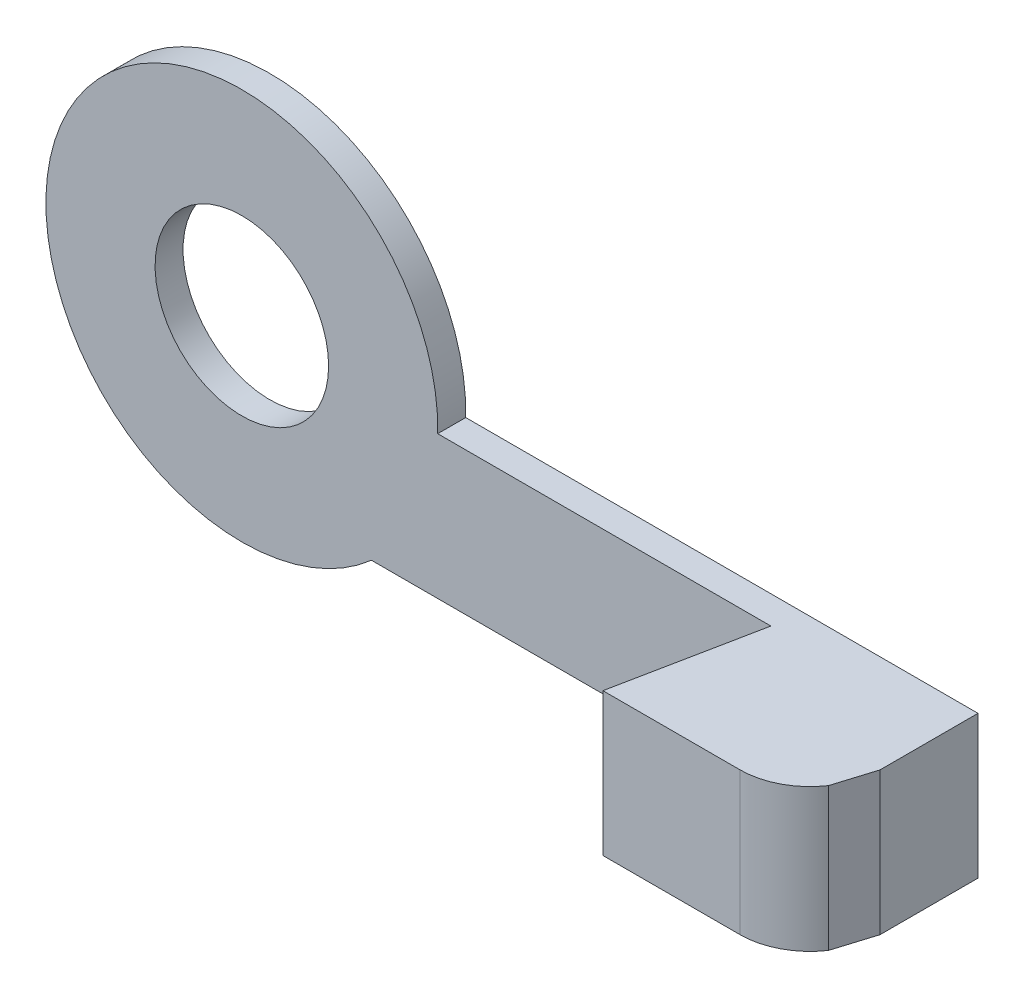
SolidWorks part; units mm, degrees
ref_plane "Front" through (0, 0, 0) normal (0, 0, 1) x (1, 0, 0)
ref_plane "Top" through (0, 0, 0) normal (0, 1, 0) x (1, 0, 0)
ref_plane "Right" through (0, 0, 0) normal (1, 0, 0) x (0, 0, -1)
sketch "Sketch3" plane through (0, 0, 0) normal (0, 1, 0) x (1, 0, 0)
  line L0 (0, -2.5) -> (-3.9, -2.5)
  line L1 (-3.9, -2.5) -> (-3.9, 3.5)
  line L2 (-3.9, 3.5) -> (-1, 3.5)
  arc A0 (2.5, 0) -> (0, -2.5) centre (0, 0) cw
  arc A1 (-1, 3.5) -> (2.5, 0) centre (-1, 0) cw
  dimension "D1" = 2.5
  dimension "D2" = 6.4
  dimension "D3" = 6
extrude "Boss-Extrude1" add sketch "Sketch3" along normal blind 5.1
sketch "Sketch4" plane through (-3.9, 0, 0) normal (-1, 0, 0) x (0, 0, 1)
  line L1 (-3.5, 5.1) -> (-2.5, 5.1)
  line L2 (-3.5, 5.1) -> (-3.5, 0)
  line L3 (-3.5, 0) -> (-2.5, 0)
  line L4 (-2.5, 5.1) -> (-2.5, 0)
  dimension "D1" = 1
extrude "Boss-Extrude2" add sketch "Sketch4" along normal blind 18.9
sketch "Sketch5" plane through (0, 0, -3.5) normal (0, 0, -1) x (-1, 0, 0)
  line L0 (22.8, 5.1) -> (22.8, 0) construction
  line L2 (1, 5.1) -> (22.8, 5.1) construction
  circle A0 centre (22.8, 5.25) radius 7
  dimension "D2" = 14
  dimension "D1" = 0.15
extrude "Boss-Extrude3" add sketch "Sketch5" against normal blind 1
sketch "Sketch6" plane through (0, 0, -2.5) normal (0, 0, 1) x (1, 0, 0)
  circle A0 centre (-22.8, 5.25) radius 3.1
  circle A1 centre (-22.8, 5.25) radius 7 construction
  dimension "D1" = 6.2
extrude "Cut-Extrude1" cut sketch "Sketch6" against normal through all both and the other way through all
sketch "Sketch7" plane through (0, 0, 0) normal (0, -1, 0) x (1, 0, 0)
  line L3 (-3.9, -2.5) -> (-3.9, 2.5)
  line L4 (-3.9, 2.5) -> (-4.9, 2.5)
  line L5 (-4.9, 2.5) -> (-3.9, -2.5)
  dimension "D1" = 1
extrude "Boss-Extrude4" add sketch "Sketch7" against normal up to surface (5.1 mm away) up to face at (-5.2372, 5.1, -1.0296)
sketch "Sketch8" plane through (0, 5.1, 0) normal (0, 1, 0) x (1, 0, 0)
  line L0 (2.5, 0) -> (0.957, -5)
  line L1 (0.957, -5) -> (5.957, -5)
  line L2 (5.957, -5) -> (5.957, 0)
  line L3 (5.957, 0) -> (2.5, 0)
  line L4 (-4.9, -2.5) -> (0, -2.5) construction
  dimension "D1" = 72.85
  dimension "D2" = 5
  dimension "D3" = 5
extrude "Cut-Extrude2" cut sketch "Sketch8" against normal blind 10
sketch "Sketch9" plane through (0, 0, 0) normal (0, 1, 0) x (1, 0, 0)
  line L1 (2.5, 3.5) -> (-1, 3.5)
  line L2 (-1, 3.5) -> (2.5, 0)
  line L4 (2.5, 0) -> (2.5, 3.5)
  arc A0 (2.5, 0) -> (-1, 3.5) centre (-1, 0) ccw construction
  point P8 (0, 0)
  point P10 (3.5801, 3.5)
extrude "Boss-Extrude5" add sketch "Sketch9" along normal up to surface (5.1 mm away) up to face at (-4.4972, 5.1, -0.7575)
